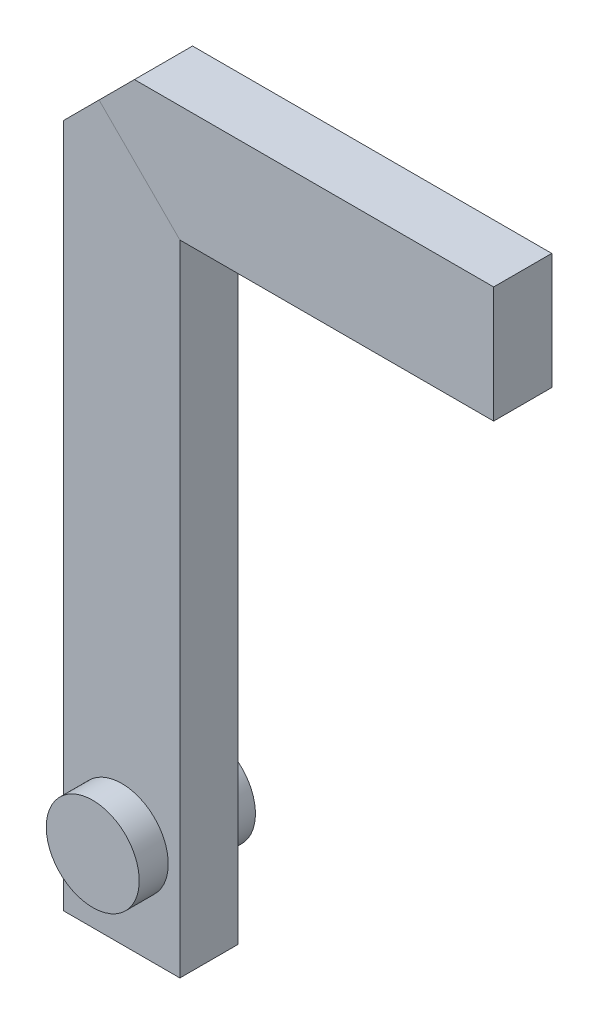
SolidWorks part; units mm, degrees
ref_plane "Front Plane" through (0, 0, 0) normal (0, 0, 1) x (1, 0, 0)
ref_plane "Top Plane" through (0, 0, 0) normal (0, 1, 0) x (1, 0, 0)
ref_plane "Right Plane" through (0, 0, 0) normal (1, 0, 0) x (0, 0, -1)
sketch "Sketch1" plane through (0, 0, 0) normal (0, 0, 1) x (1, 0, 0)
  line L0 (0, 0) -> (0, 38.1)
  line L1 (0, -55) -> (0, 55) construction
  line L2 (0, 38.1) -> (20.32, 38.1)
  dimension "D1" = 38.1
  dimension "D2" = 20.32
sketch3d "3DSketch2"
  line L1 (20.32, 34.925, -1.5875) -> (20.32, 41.275, -1.5875)
  line L2 (20.32, 34.925, -1.5875) -> (20.32, 34.925, 1.5875)
  line L3 (20.32, 34.925, 1.5875) -> (20.32, 41.275, 1.5875)
  line L4 (20.32, 41.275, -1.5875) -> (20.32, 41.275, 1.5875)
  line L5 (20.32, 34.925, -1.5875) -> (20.32, 41.275, 1.5875) construction
  line L6 (20.32, 34.925, 1.5875) -> (20.32, 41.275, -1.5875) construction
  point P0 (20.32, 38.1, 0)
  dimension "D1" = 6.35
  dimension "D2" = 3.175
sweep "Sweep1" add profiles "3DSketch2" path "Sketch1"
sketch "Sketch2" plane through (0, 0, 1.5875) normal (0, 0, 1) x (1, 0, 0)
  line L0 (3.175, 34.925) -> (-3.175, 41.275)
  line L1 (-3.175, 37.4091) -> (0.6909, 41.275)
  line L3 (-3.175, 0) -> (-3.175, 41.275) construction
  line L5 (-3.175, 41.275) -> (20.32, 41.275) construction
  line L6 (-3.175, 37.4091) -> (-3.175, 41.275)
  line L7 (0.6909, 41.275) -> (-3.175, 41.275)
  line M4 (-3.175, 41.275) -> (-3.175, 0)
extrude "Cut-Extrude1" cut sketch "Sketch2" against normal through all contours L1 L0 M4 | L1 L7 L0 region at (-2.5307, 39.342, 1.5875) region at (-1.242, 40.6307, 1.5875)
sketch "Sketch3" plane through (0, 0, 1.5875) normal (0, 0, 1) x (1, 0, 0)
  line L0 (0, 0) -> (0, 5.08)
  line L1 (0, -1.7463) -> (0, 1.7463) construction
  circle A0 centre (0, 5.08) radius 2.54
  dimension "D1" = 5.08
extrude "Boss-Extrude1" add sketch "Sketch3" against normal blind 1.5875 and the other way blind 4.7625 from offset 3.175 contours A0 region at (1.7453, 3.3347, 1.5875) offset against normal yes
